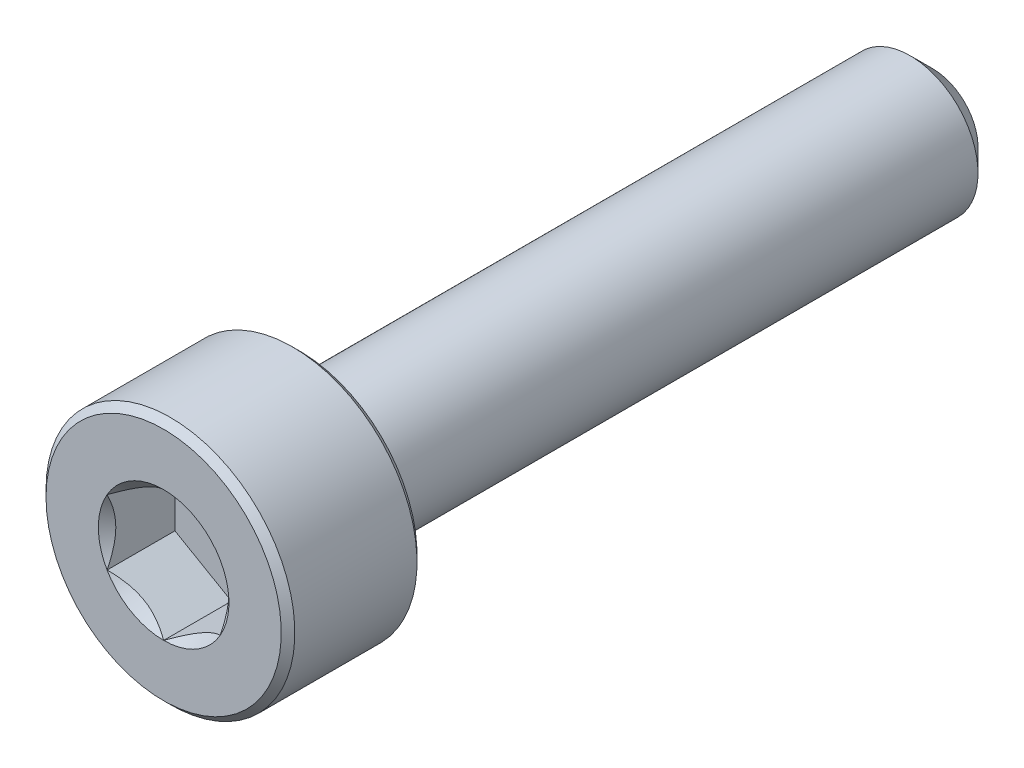
SolidWorks part; units mm, degrees
ref_plane "Front Plane" through (0, 0, 0) normal (0, 0, 1) x (1, 0, 0)
ref_plane "Top Plane" through (0, 0, 0) normal (0, 1, 0) x (1, 0, 0)
ref_plane "Right Plane" through (0, 0, 0) normal (1, 0, 0) x (0, 0, -1)
sketch "Sketch1" plane through (0, 0, 0) normal (1, 0, 0) x (0, 0, -1)
  line L0 (-8.5, 0) -> (8.5, 0) construction
  line L1 (8.5, 0) -> (8.5, 1) construction
  line L2 (8.5, 1) -> (8, 1.5) construction
  line L3 (8, 1.5) -> (-5.5, 1.5) construction
  line L5 (-5.5, 1.5) -> (-5.5, 2.75) construction
  line L6 (-5.5, 2.75) -> (-8.5, 2.75) construction
  line L7 (-8.5, 2.75) -> (-8.5, 0) construction
  line L8 (8.5, 1) -> (8.5, 1.5) construction
  line L9 (8.4687, 1.5541) -> (8.7187, 1.1211) construction
  line L10 (8.7187, 1.1211) -> (8.9688, 1.5541) construction
  line L11 (8.9688, 1.5541) -> (8.4687, 1.5541) construction
  line L12 (8.7188, 1.5541) -> (8.7188, 1.5) construction
  line L13 (8.7187, 1.1211) -> (8.7187, 1.1752) construction
  line L14 (8.6875, 1.1752) -> (8.75, 1.1752) construction
  line L15 (8.5, 1.5) -> (8.9375, 1.5) construction
  line L16 (8.4844, 1.5271) -> (8.9531, 1.5271) construction
  line L17 (8.5, 0) -> (8.5, -1.5) construction
  line L18 (-5.65, 2.75) -> (-5.5, 2.6) construction
  line L19 (-8.35, 2.75) -> (-8.5, 2.6) construction
  point P0 (-8.5, 1.25)
  point P3 (6.75, 1.5)
  point P4 (0, 0)
  point P22 (8.7187, 1.1752)
  point P24 (-5.5, 1.5)
  point P25 (8.7188, 1.5)
  point P28 (8.7188, 1.5271)
  point P29 (6.75, -1.5)
  point P31 (-7, 2.75)
  point P37 (-6.025, 2.75)
  point P38 (-8.275, 2.75)
  point P41 (-7, 0)
  dimension "head height" = 3
  dimension "D1" = 45
  dimension "Head Diameter" = 5.5
  dimension "Thread Size" = 3
  dimension "drive size" = 2.5
  dimension "Thread Pitch" = 0.5
  dimension "D2" = 0.0625
  dimension "D3" = 0.5
  dimension "D4" = 1.75
  dimension "D7" = 0.15
  dimension "D8" = 0.15
  dimension "D9" = 0.15
  dimension "D10" = 0.075
  dimension "D11" = 0.375
  dimension "length" = 14
  dimension "Drive Depth" = 1.5
sketch "Sketch2" plane through (0, 0, 0) normal (1, 0, 0) x (0, 0, -1)
  line L1 (-8.35, 2.75) -> (-5.65, 2.75)
  line L4 (8, 1.5) -> (8.5, 1)
  line L5 (8.5, 1) -> (8.5, 0)
  line L6 (-5.65, 2.75) -> (-5.5, 2.6) construction
  line L7 (8.5, 0) -> (-8.5, 0)
  line L8 (-8.35, 2.75) -> (-8.5, 2.6) construction
  line L9 (-5.65, 2.75) -> (-5.5, 2.6)
  line L10 (-8.35, 2.75) -> (-8.5, 2.6)
  line L11 (-8.5, 2.6) -> (-8.5, 0)
  line L12 (-5.5, 2.6) -> (-5.5, 1.5)
  line L13 (-5.5, 1.5) -> (8, 1.5)
revolve "Revolve1" add sketch "Sketch2" angle 360 about L7
sketch "Sketch3" plane through (0, 0, 8.5) normal (0, 0, 1) x (1, 0, 0)
  line L1 (0, 1.4434) -> (-1.25, 0.7217)
  line L2 (-1.25, 0.7217) -> (-1.25, -0.7217)
  line L3 (-1.25, -0.7217) -> (0, -1.4434)
  line L4 (0, -1.4434) -> (1.25, -0.7217)
  line L5 (1.25, -0.7217) -> (1.25, 0.7217)
  line L6 (1.25, 0.7217) -> (0, 1.4434)
  circle A0 centre (0, 0) radius 1.25 construction
  dimension "D1" = 2.5
extrude "Cut-Extrude1" cut sketch "Sketch3" against normal up to vertex (1.5 mm away) up to point (0, 0, 7)
sketch "Sketch4" plane through (0, 0, 8.5) normal (0, 0, 1) x (1, 0, 0)
  circle A0 centre (0, 0) radius 1.4434
extrude "Cut-Extrude2" cut sketch "Sketch4" against normal blind 0.5 draft 45
ref_plane "Plane1" [suppressed] through (0, 0, 5.5) normal (0, 0, 1) x (1, 0, 0)
split "Split1" [suppressed] bodies to split 106
sketch "Sketch6" [suppressed] plane through (0, 0, -8.5) normal (0, 0, -1) x (-1, 0, 0)
  circle A0 centre (0, 0) radius 1.5
curve "Helix/Spiral1" [suppressed] pitch 0.5 height 14.5 turns 29
sketch "Sketch7" [suppressed] plane through (0, 0, 0) normal (1, 0, 0) x (0, 0, -1)
  line L0 (8.4844, 1.5271) -> (8.9531, 1.5271)
  line L1 (8.9531, 1.5271) -> (8.75, 1.1752)
  line L2 (8.75, 1.1752) -> (8.6875, 1.1752)
  line L3 (8.6875, 1.1752) -> (8.4844, 1.5271)
sweep "Cut-Sweep1" [suppressed] cut profiles "Sketch7" path "Helix/Spiral1"
sketch "Sketch8" [suppressed] plane through (0, 0, 5.5) normal (0, 0, -1) x (-1, 0, 0)
  circle A0 centre (0, 0) radius 1.5
extrude "Boss-Extrude1" [suppressed] add sketch "Sketch8" along normal through all draft 45
ref_plane "Plane2" [suppressed] through (0, 0, 7) normal (0, 0, 1) x (1, 0, 0)
sketch "Sketch9" [suppressed] plane through (0, 0, 7) normal (0, 0, 1) x (1, 0, 0)
  line L0 (0, 2.6744) -> (0.072, 2.7491)
  line L1 (0, 2.6744) -> (-0.072, 2.7491)
  line L2 (0, 2.75) -> (0, 0) construction
  line L3 (-0.072, 2.7491) -> (0, 0) construction
  line L4 (0, 0) -> (0.072, 2.7491) construction
  arc A0 (0.072, 2.7491) -> (-0.072, 2.7491) centre (0, 0) ccw
  circle A1 centre (0, 0) radius 2.6744 construction
  dimension "D1" = 5.5
  dimension "D2" = 5.3487
  dimension "D3" = 3
extrude "Cut-Extrude4" [suppressed] cut sketch "Sketch9" against normal up to vertex and the other way up to vertex
pattern_circular "CirPattern2" [suppressed] count 96 over 360 about axis through (0, 0, 8.5) along (0, 0, -1) of bodies 113
equation "\"D2@Sketch1\" = \"Thread Pitch@Sketch1\" / 8"
equation "\"D3@Sketch1\" = \"Thread Pitch@Sketch1\""
equation "\"D3@Helix/Spiral1\" = \"length@Sketch1\" + \"Thread Pitch@Sketch1\""
equation "\"D4@Helix/Spiral1\" = \"Thread Pitch@Sketch1\""
equation "\"D4@Sketch1\" = \"Thread Pitch@Sketch1\" * 3.5"
equation "\"D7@Sketch1\"=\"head height@Sketch1\"*.05"
equation "\"D8@Sketch1\"=\"D7@Sketch1\""
equation "\"D9@Sketch1\"=\"D7@Sketch1\""
equation "\"D10@Sketch1\"=\"D7@Sketch1\"/2"
equation "\"D11@Sketch1\"=\"D10@Sketch1\"*5"
equation "\"D1@CirPattern2\"=( 360 / \"D3@Sketch9\" )*0.8"
equation "\"D1@Sketch3\" = \"drive size@Sketch1\""
equation "\"D2@Sketch9\"=\"Head Diameter@Sketch1\" * 0.9725"
